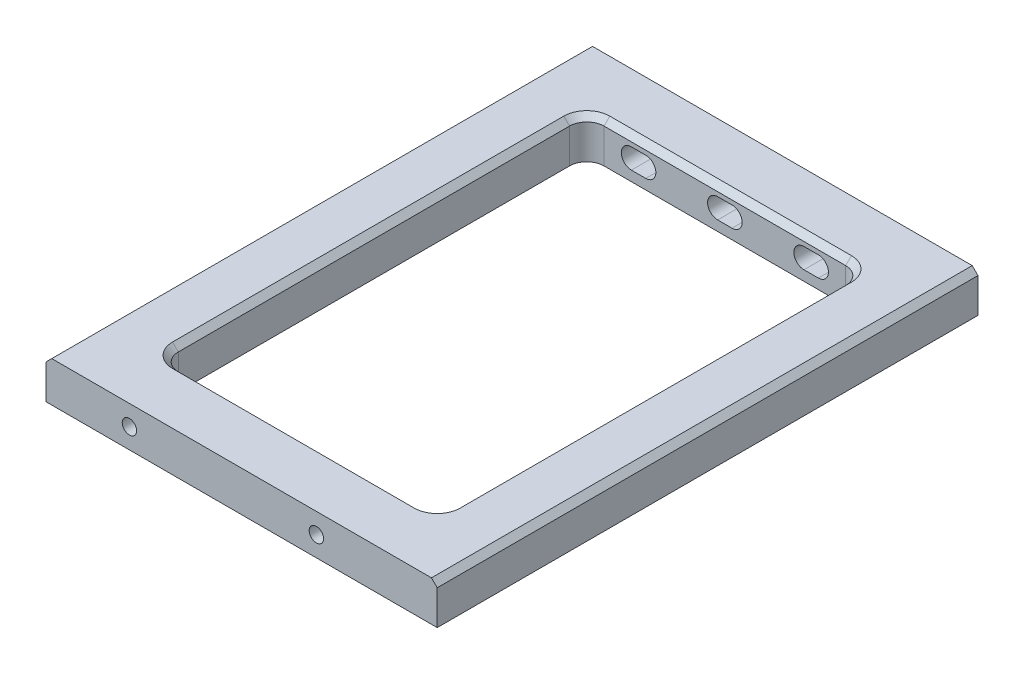
SolidWorks part; units mm, degrees
other "Markup1"
sketch "Sketch11" plane through (-148, 207, 138) normal (-0.4174, 0.5856, 0.6948) x (0.7295, -0.24, 0.6405)
ref_plane "Front Plane" through (0, 0, 0) normal (0, 0, 1) x (1, 0, 0)
ref_plane "Top Plane" through (0, 0, 0) normal (0, 1, 0) x (1, 0, 0)
ref_plane "Right Plane" through (0, 0, 0) normal (1, 0, 0) x (0, 0, -1)
sketch "Sketch1" plane through (0, 0, 0) normal (0, 0, 1) x (1, 0, 0)
  line L1 (-148, 230) -> (-148, 165) construction
  line L4 (-148, 207) -> (-21, 207)
  line L7 (-148, 197.5) -> (-148, 192.5) construction
  line L8 (-148, 197.5) -> (-148, 192.5)
  line L9 (-148, 192.5) -> (-148, 193)
  line L10 (-148, 197.5) -> (-148, 207)
  line L11 (-148, 193) -> (-24, 193)
  line L13 (-148, 207) -> (-21, 207)
  line L16 (-21, 207) -> (-12, 207)
  line L17 (-12, 207) -> (-12, 193)
  line L18 (-12, 193) -> (-24, 193)
extrude "Boss-Extrude1" add sketch "Sketch1" along normal offset from surface (188 mm away) 12 contours L4 L10 L8 L9 L11 region at (-80, 200, 0)
sketch "Sketch3" plane through (0, 207, 0) normal (0, 1, 0) x (1, 0, 0)
  line L0 (-128, -30) -> (-128, -20)
  line L1 (-128, -108) -> (-128, -168)
  line L2 (-128, -168) -> (-118, -168)
  line L3 (-54, -168) -> (-32, -168)
  line L4 (-32, -168) -> (-32, -20)
  line L5 (-32, -168) -> (-32, -20)
  line L6 (-32, -20) -> (-128, -20)
  line L7 (-32, -20) -> (-128, -20)
  line L12 (-128, -20) -> (-128, -168)
  line L13 (-128, -20) -> (-128, -168)
  line L23 (-128, -168) -> (-32, -168)
  line L27 (-118, -168) -> (-54, -168)
  dimension "D1" = 20
extrude "Cut-Extrude1" cut sketch "Sketch3" against normal through all contours L7 L13 L27 region at (-80, 207, 94)
sketch "Sketch5" plane through (0, 0, 20) normal (0, 0, 1) x (1, 0, 0)
  circle A3 centre (-110, 200) radius 3
  circle A4 centre (-80, 200) radius 3
  circle A5 centre (-50, 200) radius 3
hole_wizard "Ø6.0mm Dowel Slot1" positions "Sketch6" profile "Sketch7" size "Ø6.0" standard "ANSI Metric" slot yes end condition through all
sketch "Sketch6" plane through (0, 0, 20) normal (0, 0, 1) x (1, 0, 0)
  line L0 (-116, 200) -> (-104, 200) construction
  point P12 (-110, 200)
  point P15 (-80, 200)
  point P18 (-50, 200)
  dimension "D1" = 12
sketch "Sketch7" plane through (-110, 200, 20) normal (1, 0, 0) x (0, -1, 0)
  line L0 (0, 0) -> (0, 20)
  line L1 (0, 20) -> (3.5, 20)
  line L2 (3.5, 20) -> (3.5, 0)
  line L5 (3.5, 0) -> (0, 0)
  line L11 (0, -6.35) -> (0, 107.95) construction
  dimension "Thru Hole Dia." = 7
  dimension "Thru Hole Depth" = 20
sketch "Sketch8" plane through (0, 0, 188) normal (0, 0, 1) x (1, 0, 0)
  line L0 (-48, 200) -> (-54, 200)
  line L2 (-148, 200) -> (-119, 200)
hole_wizard "M6x1.0 Tapped Hole1" positions "Sketch9" profile "Sketch10" tap size "M6x1.0" standard "ANSI Metric"
sketch "Sketch9" plane through (0, 0, 188) normal (0, 0, 1) x (1, 0, 0)
  point P0 (-119, 200)
  point P3 (-54, 200)
sketch "Sketch10" plane through (-119, 200, 188) normal (1, 0, 0) x (0, -1, 0)
  line L0 (0, 0) -> (0, 23)
  line L1 (0, 23) -> (2.5, 21.4978)
  line L2 (2.5, 21.4978) -> (2.5, 0)
  line L5 (2.5, 0) -> (0, 0)
  line L10 (0, 23) -> (-2.5, 21.4978) construction
  line L11 (0, -6.35) -> (0, 107.95) construction
  dimension "Tap Drill Dia." = 5
  dimension "Tap Drill Depth" = 23
  dimension "Drill Angle" = 118
cosmetic thread "Hole Thread1" parameters "D1"=20, "D2"=6
cosmetic thread "Hole Thread2" parameters "D1"=20, "D2"=6
fillet "Fillet1" radius 6 4 edges at (-128, 200, 168) (-128, 200, 20) (-32, 200, 168) (-32, 200, 20)
chamfer "Chamfer1" distance 2 angle 45 10 edges at (-128, 207, 94) (-80, 207, 168) (-148, 207, 94) (-80, 207, 20) (-32, 207, 94) (-12, 207, 94) (-126.2426, 207, 166.2426) (-126.2426, 207, 21.7574) (-33.7574, 207, 166.2426) (-33.7574, 207, 21.7574)
